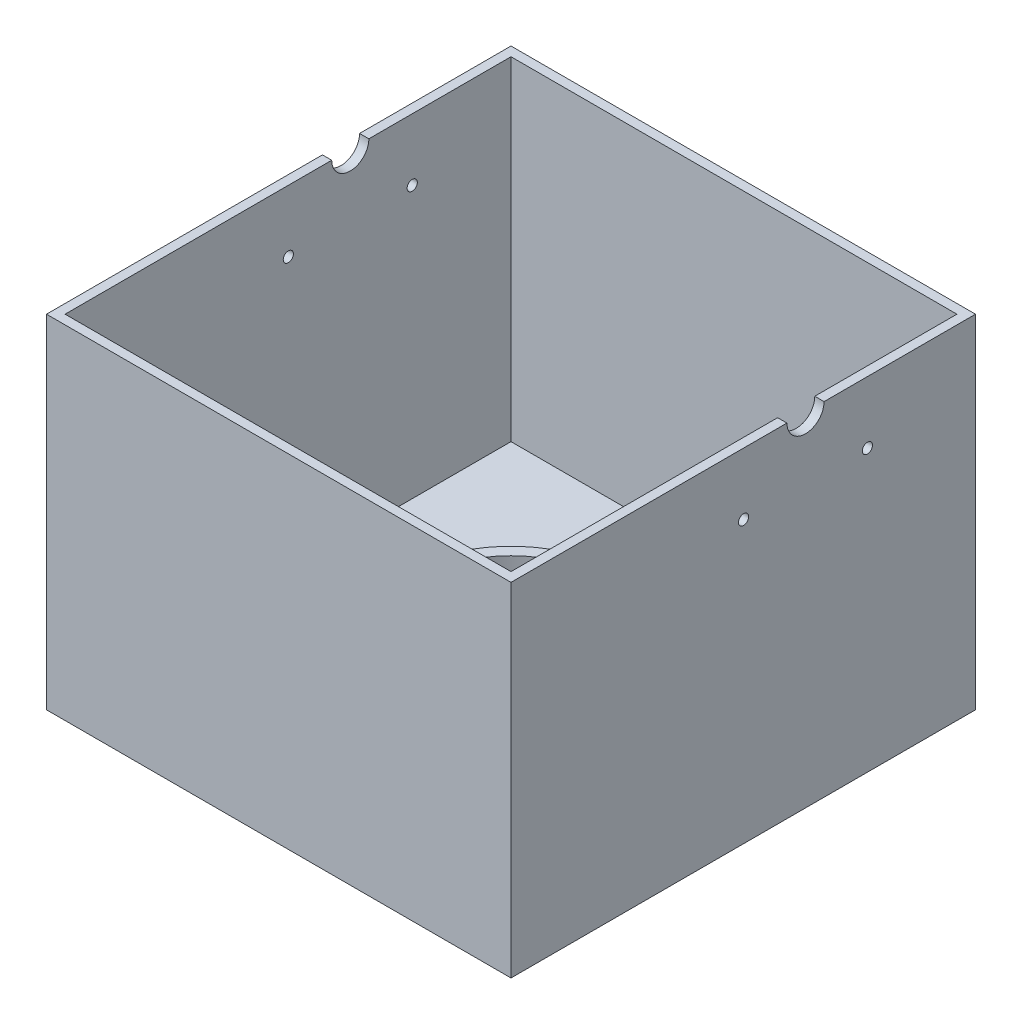
SolidWorks part; units mm, degrees
other "标注1"
sketch "草图10" plane through (-75, 110.65, 75) normal (-0.0015, 0.991, 0.1342) x (0.9966, 0.0125, -0.0811)
ref_plane "前视基准面" through (0, 0, 0) normal (0, 0, 1) x (1, 0, 0)
ref_plane "上视基准面" through (0, 0, 0) normal (0, 1, 0) x (1, 0, 0)
ref_plane "右视基准面" through (0, 0, 0) normal (1, 0, 0) x (0, 0, -1)
sketch "草图1" plane through (0, 0, 0) normal (0, 1, 0) x (1, 0, 0)
  line L1 (-75, 75) -> (75, 75)
  line L2 (-75, 75) -> (-75, -75)
  line L3 (-75, -75) -> (75, -75)
  line L4 (75, 75) -> (75, -75)
  line L5 (-75, 75) -> (75, -75) construction
  line L6 (-75, -75) -> (75, 75) construction
  point P0 (0, 0)
  dimension "D1" = 150
  dimension "D2" = 150
extrude "凸台-拉伸1" add sketch "草图1" along normal blind 3
sketch "草图2" plane through (0, 3, 0) normal (0, 1, 0) x (1, 0, 0)
  line L1 (75, -75) -> (-75, -75)
  line L2 (75, -75) -> (75, 75)
  line L3 (75, 75) -> (-75, 75)
  line L4 (-75, -75) -> (-75, 75)
  line L5 (75, -75) -> (-75, 75) construction
  line L6 (75, 75) -> (-75, -75) construction
  line L7 (72, -72) -> (-72, -72)
  line L8 (72, -72) -> (72, 72)
  line L9 (72, 72) -> (-72, 72)
  line L10 (-72, -72) -> (-72, 72)
  line L11 (72, -72) -> (-72, 72) construction
  line L12 (72, 72) -> (-72, -72) construction
  point P0 (0, 0)
  point P7 (0, 0)
  dimension "D1" = 144
extrude "凸台-拉伸2" add sketch "草图2" along normal blind 107.65
sketch "草图3" plane through (0, 0, 0) normal (0, -1, 0) x (1, 0, 0)
  circle A0 centre (0, 0) radius 31.25
  dimension "D1" = 62.5
extrude "切除-拉伸1" cut sketch "草图3" against normal blind 91
sketch "草图4" plane through (-75, 0, 0) normal (-1, 0, 0) x (0, 0, 1)
  line L0 (-75, 110.65) -> (75, 110.65) construction
  line L1 (-75, 110.65) -> (-75, 0) construction
  circle A0 centre (-20.1, 110.65) radius 6
  dimension "D1" = 12
  dimension "D2" = 54.9
extrude "切除-拉伸2" cut sketch "草图4" against normal through all
sketch "草图8" plane through (0, 3, 0) normal (0, 1, 0) x (1, 0, 0)
  circle A0 centre (0, 0) radius 31.25
  circle A1 centre (0, 0) radius 35
  dimension "D1" = 62.5
  dimension "D2" = 70
extrude "凸台-拉伸4" add sketch "草图8" along normal mid plane 36
sketch "草图9" plane through (-75, 0, 0) normal (-1, 0, 0) x (0, 0, 1)
  line L0 (-20.1, 104.65) -> (-20.1, 66.4211) construction
  line L2 (-75, 110.65) -> (-26.1, 110.65) construction
  arc A0 (-26.1, 110.65) -> (-14.1, 110.65) centre (-20.1, 110.65) ccw construction
  circle A1 centre (-40.1, 90.65) radius 1.65
  circle A2 centre (-0.1, 90.65) radius 1.65
  dimension "D1" = 3.3
  dimension "D2" = 3.3
  dimension "D3" = 40
  dimension "D4" = 20
extrude "切除-拉伸3" cut sketch "草图9" against normal through all
sketch "草图11" plane through (0, -15, 0) normal (0, -1, 0) x (1, 0, 0)
  circle A0 centre (0, 0) radius 31.25
  circle A1 centre (0, 0) radius 27.5
  dimension "D1" = 62.5
  dimension "D2" = 55
extrude "凸台-拉伸5" add sketch "草图11" against normal blind 3
